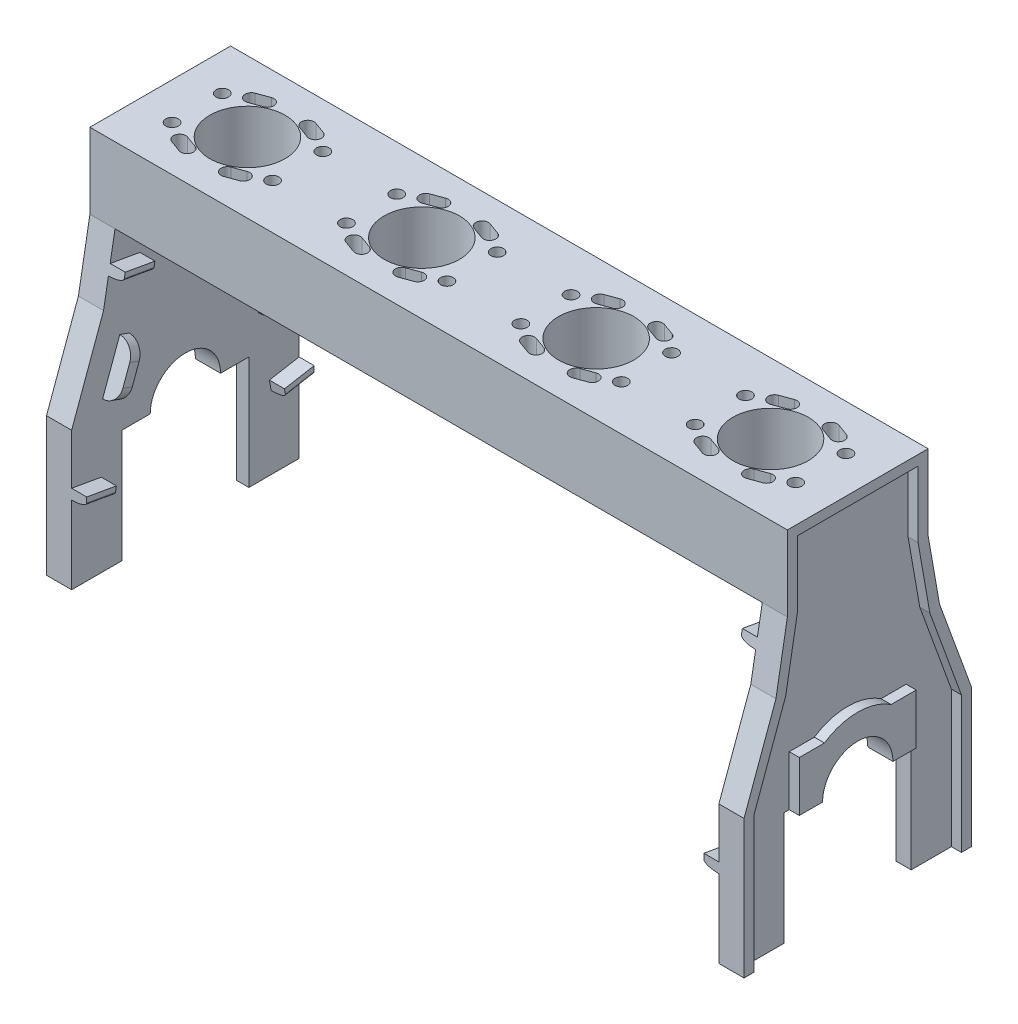
SolidWorks part; units mm, degrees
ref_plane "Front Plane" through (0, 0, 0) normal (0, 0, 1) x (1, 0, 0)
ref_plane "Top Plane" through (0, 0, 0) normal (0, 1, 0) x (1, 0, 0)
ref_plane "Right Plane" through (0, 0, 0) normal (1, 0, 0) x (0, 0, -1)
sketch "Sketch1" plane through (0, 0, 0) normal (0, 1, 0) x (1, 0, 0)
  line L0 (-313.6952, 0) -> (313.6952, 0) construction
  line L1 (-308.483, 35.56) -> (44.069, 35.56)
  line L2 (-308.483, 35.56) -> (-308.483, -35.56)
  line L3 (-308.483, -35.56) -> (44.069, -35.56)
  line L4 (44.069, 35.56) -> (44.069, -35.56)
  line L5 (0, 0) -> (0, -80.8199) construction
  line L6 (15.0411, -15.1646) -> (9.0741, -17.3365)
  line L7 (17.213, -21.1317) -> (11.2459, -23.3035)
  line L8 (16.127, -18.1482) -> (10.16, -20.32) construction
  line L9 (-17.213, -21.1317) -> (-11.2459, -23.3035)
  line L10 (-15.0411, -15.1646) -> (-9.0741, -17.3365)
  line L11 (17.213, 21.1317) -> (11.2459, 23.3035)
  line L12 (15.0411, 15.1646) -> (9.0741, 17.3365)
  line L13 (-15.0411, 15.1646) -> (-9.0741, 17.3365)
  line L14 (-17.213, 21.1317) -> (-11.2459, 23.3035)
  line L15 (-103.1791, 15.1646) -> (-97.2121, 17.3365)
  line L16 (-105.351, 21.1317) -> (-99.3839, 23.3035)
  line L17 (-70.925, 21.1317) -> (-76.8921, 23.3035)
  line L18 (-73.0969, 15.1646) -> (-79.0639, 17.3365)
  line L19 (-105.351, -21.1317) -> (-99.3839, -23.3035)
  line L20 (-103.1791, -15.1646) -> (-97.2121, -17.3365)
  line L21 (-73.0969, -15.1646) -> (-79.0639, -17.3365)
  line L22 (-70.925, -21.1317) -> (-76.8921, -23.3035)
  line L23 (-191.3171, 15.1646) -> (-185.3501, 17.3365)
  line L24 (-193.489, 21.1317) -> (-187.5219, 23.3035)
  line L25 (-159.063, 21.1317) -> (-165.0301, 23.3035)
  line L26 (-161.2349, 15.1646) -> (-167.2019, 17.3365)
  line L27 (-193.489, -21.1317) -> (-187.5219, -23.3035)
  line L28 (-191.3171, -15.1646) -> (-185.3501, -17.3365)
  line L29 (-161.2349, -15.1646) -> (-167.2019, -17.3365)
  line L30 (-159.063, -21.1317) -> (-165.0301, -23.3035)
  line L31 (-279.4551, 15.1646) -> (-273.4881, 17.3365)
  line L32 (-281.627, 21.1317) -> (-275.6599, 23.3035)
  line L33 (-247.201, 21.1317) -> (-253.1681, 23.3035)
  line L34 (-249.3729, 15.1646) -> (-255.3399, 17.3365)
  line L35 (-281.627, -21.1317) -> (-275.6599, -23.3035)
  line L36 (-279.4551, -15.1646) -> (-273.4881, -17.3365)
  line L37 (-249.3729, -15.1646) -> (-255.3399, -17.3365)
  line L38 (-247.201, -21.1317) -> (-253.1681, -23.3035)
  circle A4 centre (0, 0) radius 19.05
  circle A9 centre (-88.138, 0) radius 19.05
  circle A10 centre (-176.276, 0) radius 19.05
  circle A11 centre (-264.414, 0) radius 19.05
  circle A12 centre (25.4, -12.7) radius 3.175
  arc A17 (17.213, -21.1317) -> (15.0411, -15.1646) centre (16.127, -18.1482) ccw
  arc A18 (11.2459, -23.3035) -> (9.0741, -17.3365) centre (10.16, -20.32) cw
  circle A19 centre (-25.4, -12.7) radius 3.175
  arc A20 (-17.213, -21.1317) -> (-15.0411, -15.1646) centre (-16.127, -18.1482) cw
  arc A21 (-11.2459, -23.3035) -> (-9.0741, -17.3365) centre (-10.16, -20.32) ccw
  circle A22 centre (25.4, 12.7) radius 3.175
  arc A23 (17.213, 21.1317) -> (15.0411, 15.1646) centre (16.127, 18.1482) cw
  arc A24 (11.2459, 23.3035) -> (9.0741, 17.3365) centre (10.16, 20.32) ccw
  arc A25 (-17.213, 21.1317) -> (-15.0411, 15.1646) centre (-16.127, 18.1482) ccw
  arc A26 (-11.2459, 23.3035) -> (-9.0741, 17.3365) centre (-10.16, 20.32) cw
  circle A27 centre (-25.4, 12.7) radius 3.175
  circle A28 centre (-113.538, 12.7) radius 3.175
  arc A29 (-105.351, 21.1317) -> (-103.1791, 15.1646) centre (-104.265, 18.1482) ccw
  arc A30 (-99.3839, 23.3035) -> (-97.2121, 17.3365) centre (-98.298, 20.32) cw
  arc A31 (-76.8921, 23.3035) -> (-79.0639, 17.3365) centre (-77.978, 20.32) ccw
  arc A32 (-70.925, 21.1317) -> (-73.0969, 15.1646) centre (-72.011, 18.1482) cw
  circle A33 centre (-62.738, 12.7) radius 3.175
  arc A34 (-99.3839, -23.3035) -> (-97.2121, -17.3365) centre (-98.298, -20.32) ccw
  arc A35 (-105.351, -21.1317) -> (-103.1791, -15.1646) centre (-104.265, -18.1482) cw
  circle A36 centre (-113.538, -12.7) radius 3.175
  arc A37 (-76.8921, -23.3035) -> (-79.0639, -17.3365) centre (-77.978, -20.32) cw
  arc A38 (-70.925, -21.1317) -> (-73.0969, -15.1646) centre (-72.011, -18.1482) ccw
  circle A39 centre (-62.738, -12.7) radius 3.175
  circle A40 centre (-201.676, 12.7) radius 3.175
  arc A41 (-193.489, 21.1317) -> (-191.3171, 15.1646) centre (-192.403, 18.1482) ccw
  arc A42 (-187.5219, 23.3035) -> (-185.3501, 17.3365) centre (-186.436, 20.32) cw
  arc A43 (-165.0301, 23.3035) -> (-167.2019, 17.3365) centre (-166.116, 20.32) ccw
  arc A44 (-159.063, 21.1317) -> (-161.2349, 15.1646) centre (-160.149, 18.1482) cw
  circle A45 centre (-150.876, 12.7) radius 3.175
  arc A46 (-187.5219, -23.3035) -> (-185.3501, -17.3365) centre (-186.436, -20.32) ccw
  arc A47 (-193.489, -21.1317) -> (-191.3171, -15.1646) centre (-192.403, -18.1482) cw
  circle A48 centre (-201.676, -12.7) radius 3.175
  arc A49 (-165.0301, -23.3035) -> (-167.2019, -17.3365) centre (-166.116, -20.32) cw
  arc A50 (-159.063, -21.1317) -> (-161.2349, -15.1646) centre (-160.149, -18.1482) ccw
  circle A51 centre (-150.876, -12.7) radius 3.175
  circle A52 centre (-289.814, 12.7) radius 3.175
  arc A53 (-281.627, 21.1317) -> (-279.4551, 15.1646) centre (-280.541, 18.1482) ccw
  arc A54 (-275.6599, 23.3035) -> (-273.4881, 17.3365) centre (-274.574, 20.32) cw
  arc A55 (-253.1681, 23.3035) -> (-255.3399, 17.3365) centre (-254.254, 20.32) ccw
  arc A56 (-247.201, 21.1317) -> (-249.3729, 15.1646) centre (-248.287, 18.1482) cw
  circle A57 centre (-239.014, 12.7) radius 3.175
  arc A58 (-275.6599, -23.3035) -> (-273.4881, -17.3365) centre (-274.574, -20.32) ccw
  arc A59 (-281.627, -21.1317) -> (-279.4551, -15.1646) centre (-280.541, -18.1482) cw
  circle A60 centre (-289.814, -12.7) radius 3.175
  arc A61 (-253.1681, -23.3035) -> (-255.3399, -17.3365) centre (-254.254, -20.32) cw
  arc A62 (-247.201, -21.1317) -> (-249.3729, -15.1646) centre (-248.287, -18.1482) ccw
  circle A63 centre (-239.014, -12.7) radius 3.175
  point P16 (-308.483, 0)
  dimension "D1" = 38.1
  dimension "D2" = 88.138
  dimension "D3" = 6.35
  dimension "D4" = 35.56
  dimension "D8" = 6.35
  dimension "D10" = 10.16
  dimension "D9" = 6.35
  dimension "D16" = 4
  dimension "D5" = 44.069
  dimension "D6" = 12.7
  dimension "D7" = 25.4
  dimension "D11" = 20.32
  dimension "D12" = 70
  dimension "D13" = 62.738
  dimension "D14" = 352.552
  dimension "D15" = 4
extrude "Boss-Extrude1" add sketch "Sketch1" along normal blind 38.1
sketch "Sketch2" plane through (44.069, 0, 0) normal (1, 0, 0) x (0, 0, -1)
  line L0 (-35.56, 0) -> (-41.3634, -32.9128)
  line L1 (-35.56, 0) -> (35.56, 0) construction
  line L19 (0, -72.136) -> (0, 0) construction
  line L20 (-41.3634, -32.9128) -> (-57.4885, -77.216)
  line L21 (-57.4885, -77.216) -> (-57.4885, -147.066)
  line L22 (-17.78, -89.916) -> (-32.0885, -89.916)
  line L23 (-32.0885, -89.916) -> (-32.0885, -147.066)
  line L24 (-32.0885, -147.066) -> (-57.4885, -147.066)
  line L25 (-29.5485, -89.916) -> (-29.5485, -115.316) construction
  line L26 (17.78, -89.916) -> (32.0885, -89.916)
  line L27 (32.0885, -89.916) -> (32.0885, -147.066)
  line L28 (32.0885, -147.066) -> (57.4885, -147.066)
  line L29 (57.4885, -77.216) -> (57.4885, -147.066)
  line L30 (41.3634, -32.9128) -> (57.4885, -77.216)
  line L31 (35.56, 0) -> (41.3634, -32.9128)
  line L33 (-35.56, 0) -> (35.56, 0)
  arc A0 (17.78, -89.916) -> (-17.78, -89.916) centre (0, -89.916) ccw
  dimension "D1" = 17.78
  dimension "D2" = 71.12
  dimension "D3" = 12.7
  dimension "D5" = 170
  dimension "D7" = 25.4
  dimension "D4" = 89.916
  dimension "D6" = 2.54
  dimension "D8" = 14.3085
  dimension "D9" = 100
  dimension "D10" = 57.15
extrude "Boss-Extrude2" add sketch "Sketch2" against normal blind 12.7
sketch "Sketch3" plane through (44.069, 0, 0) normal (1, 0, 0) x (0, 0, -1)
  line L3 (-29.5485, -64.516) -> (-16.8485, -64.516)
  line L4 (16.8485, -64.516) -> (29.5485, -64.516)
  line L9 (-29.5485, -64.516) -> (-29.5485, -89.916)
  line L12 (29.5485, -64.516) -> (29.5485, -89.916)
  line L76 (0, 0) -> (0, -72.136) construction
  line L94 (-29.5485, -89.916) -> (-32.0885, -89.916)
  line L96 (-32.0885, -89.916) -> (-32.0885, -147.066)
  line L101 (-32.0885, -147.066) -> (-52.4085, -147.066)
  line L102 (29.5485, -89.916) -> (32.0885, -89.916)
  line L107 (32.0885, -89.916) -> (32.0885, -147.066) construction
  line L108 (17.78, -89.916) -> (32.0885, -89.916) construction
  line L109 (32.0885, -89.916) -> (32.0885, -147.066)
  line L110 (32.0885, -147.066) -> (57.4885, -147.066) construction
  line L111 (32.0885, -147.066) -> (52.4085, -147.066)
  line L112 (30.48, -0.4444) -> (30.48, 33.02)
  line L113 (36.4378, -34.2327) -> (30.48, -0.4444)
  line L114 (52.4085, -78.1117) -> (36.4378, -34.2327)
  line L115 (52.4085, -147.066) -> (52.4085, -78.1117)
  line L116 (-52.4085, -78.1117) -> (-52.4085, -147.066)
  line L117 (-36.4378, -34.2327) -> (-52.4085, -78.1117)
  line L118 (-30.48, -0.4444) -> (-36.4378, -34.2327)
  line L119 (-30.48, 33.02) -> (-30.48, -0.4444)
  line L120 (30.48, 33.02) -> (-30.48, 33.02)
  line L121 (30.48, -0.4444) -> (30.48, 33.02)
  line L122 (36.4378, -34.2327) -> (30.48, -0.4444)
  line L123 (52.4085, -78.1117) -> (36.4378, -34.2327)
  line L124 (52.4085, -147.066) -> (52.4085, -78.1117)
  line L125 (-52.4085, -78.1117) -> (-52.4085, -147.066)
  line L126 (-36.4378, -34.2327) -> (-52.4085, -78.1117)
  line L127 (-30.48, -0.4444) -> (-36.4378, -34.2327)
  line L128 (-30.48, 33.02) -> (-30.48, -0.4444)
  line L129 (30.48, 33.02) -> (-30.48, 33.02)
  arc A2 (16.8485, -64.516) -> (-16.8485, -64.516) centre (0, -89.916) ccw
  dimension "D6" = 25.4
  dimension "D2" = 30.48
  dimension "D3" = 25.4
  dimension "D4" = 12.7
  dimension "D5" = 12.7
  dimension "D1" = 5.08
extrude "Cut-Extrude1" cut sketch "Sketch3" against normal blind 5.08
sketch "Sketch5" plane through (-308.483, 0, 0) normal (-1, 0, 0) x (0, 0, 1)
  line L7 (17.78, -89.916) -> (32.0885, -89.916)
  line L8 (17.78, -89.916) -> (32.0885, -89.916)
  line L9 (32.0885, -89.916) -> (32.0885, -147.066)
  line L10 (35.56, 0) -> (-35.56, 0)
  line L11 (32.0885, -89.916) -> (32.0885, -147.066)
  line L12 (32.0885, -147.066) -> (57.4885, -147.066)
  line L13 (32.0885, -147.066) -> (57.4885, -147.066)
  line L17 (35.56, 0) -> (-35.56, 0)
  line L27 (57.4885, -147.066) -> (57.4885, -77.216)
  line L28 (57.4885, -147.066) -> (57.4885, -77.216)
  line L29 (57.4885, -77.216) -> (41.3634, -32.9128)
  line L30 (57.4885, -77.216) -> (41.3634, -32.9128)
  line L31 (41.3634, -32.9128) -> (35.56, 0)
  line L32 (41.3634, -32.9128) -> (35.56, 0)
  line L33 (-35.56, 0) -> (-41.3634, -32.9128)
  line L34 (-35.56, 0) -> (-41.3634, -32.9128)
  line L35 (-41.3634, -32.9128) -> (-57.4885, -77.216)
  line L36 (-41.3634, -32.9128) -> (-57.4885, -77.216)
  line L37 (-57.4885, -77.216) -> (-57.4885, -147.066)
  line L38 (-57.4885, -77.216) -> (-57.4885, -147.066)
  line L39 (-57.4885, -147.066) -> (-32.0885, -147.066)
  line L40 (-57.4885, -147.066) -> (-32.0885, -147.066)
  line L41 (-32.0885, -147.066) -> (-32.0885, -89.916)
  line L42 (-32.0885, -147.066) -> (-32.0885, -89.916)
  line L43 (-32.0885, -89.916) -> (-17.78, -89.916)
  line L44 (-32.0885, -89.916) -> (-17.78, -89.916)
  arc A1 (17.78, -89.916) -> (-17.78, -89.916) centre (0, -89.916) ccw
  arc A2 (17.78, -89.916) -> (-17.78, -89.916) centre (0, -89.916) ccw
  dimension "D1" = 0
extrude "Boss-Extrude3" add sketch "Sketch5" against normal blind 12.7
sketch "Sketch6" plane through (-308.483, 0, 0) normal (-1, 0, 0) x (0, 0, 1)
  line L4 (29.5485, -64.516) -> (29.5485, -89.916)
  line L20 (29.5485, -64.516) -> (29.5485, -89.916)
  line L21 (16.8485, -64.516) -> (29.5485, -64.516)
  line L22 (16.8485, -64.516) -> (29.5485, -64.516)
  line L24 (-29.5485, -64.516) -> (-16.8485, -64.516)
  line L25 (-29.5485, -64.516) -> (-16.8485, -64.516)
  line L39 (-29.5485, -89.916) -> (-29.5485, -64.516)
  line L40 (-29.5485, -89.916) -> (-29.5485, -64.516)
  line L41 (-32.0885, -89.916) -> (-29.5485, -89.916)
  line L42 (-32.0885, -89.916) -> (-29.5485, -89.916)
  line L43 (-32.0885, -147.066) -> (-32.0885, -89.916)
  line L44 (-32.0885, -147.066) -> (-32.0885, -89.916)
  line L45 (-52.4085, -147.066) -> (-32.0885, -147.066)
  line L46 (-52.4085, -147.066) -> (-32.0885, -147.066)
  line L47 (-52.4085, -78.1117) -> (-52.4085, -147.066)
  line L48 (-52.4085, -78.1117) -> (-52.4085, -147.066)
  line L49 (-36.4378, -34.2327) -> (-52.4085, -78.1117)
  line L50 (-36.4378, -34.2327) -> (-52.4085, -78.1117)
  line L51 (-30.48, -0.4444) -> (-36.4378, -34.2327)
  line L52 (-30.48, -0.4444) -> (-36.4378, -34.2327)
  line L53 (-30.48, 33.02) -> (-30.48, -0.4444)
  line L54 (-30.48, 33.02) -> (-30.48, -0.4444)
  line L55 (30.48, 33.02) -> (-30.48, 33.02)
  line L56 (30.48, 33.02) -> (-30.48, 33.02)
  line L57 (30.48, -0.4444) -> (30.48, 33.02)
  line L58 (30.48, -0.4444) -> (30.48, 33.02)
  line L59 (36.4378, -34.2327) -> (30.48, -0.4444)
  line L60 (36.4378, -34.2327) -> (30.48, -0.4444)
  line L61 (52.4085, -78.1117) -> (36.4378, -34.2327)
  line L62 (52.4085, -78.1117) -> (36.4378, -34.2327)
  line L63 (52.4085, -147.066) -> (52.4085, -78.1117)
  line L64 (52.4085, -147.066) -> (52.4085, -78.1117)
  line L65 (32.0885, -147.066) -> (52.4085, -147.066)
  line L66 (32.0885, -147.066) -> (52.4085, -147.066)
  line L67 (32.0885, -89.916) -> (32.0885, -147.066)
  line L68 (32.0885, -89.916) -> (32.0885, -147.066)
  line L69 (29.5485, -89.916) -> (32.0885, -89.916)
  line L70 (29.5485, -89.916) -> (32.0885, -89.916)
  arc A1 (16.8485, -64.516) -> (-16.8485, -64.516) centre (0, -89.916) ccw
  arc A3 (16.8485, -64.516) -> (-16.8485, -64.516) centre (0, -89.916) ccw
  dimension "D1" = 0
extrude "Cut-Extrude4" cut sketch "Sketch6" against normal blind 6.35
sketch "Sketch7" plane through (0, -89.916, 0) normal (0, -1, 0) x (1, 0, 0)
  line L0 (44.069, 23.1985) -> (31.369, 23.1985) construction
  line L3 (-396.1332, 0) -> (-407.4069, 0) construction
  line L5 (-132.207, 64.7886) -> (-132.207, -75.2816) construction
  line L6 (-295.783, 35.56) -> (31.369, 35.56) construction
  line L9 (44.069, 29.5485) -> (44.069, 17.78) construction
  line L10 (44.069, 29.5485) -> (44.069, 16.8485) construction
  line L11 (31.369, 32.0885) -> (31.369, 17.78) construction
  circle A0 centre (37.719, 23.1985) radius 3.175
  circle A4 centre (37.719, -23.1985) radius 3.175
  circle A5 centre (-302.133, -23.1985) radius 3.175
  circle A6 centre (-302.133, 23.1985) radius 3.175
  point P18 (-132.207, 35.56)
  point P29 (44.069, 23.1985)
  dimension "D1" = 6.35
extrude "Cut-Extrude5" cut sketch "Sketch7" against normal offset from surface (17.78 mm away) 7.62 up to face at (41.529, -64.516, 23.1985)
sketch "Sketch8" plane through (31.369, 0, 0) normal (-1, 0, 0) x (0, 0, 1)
  line L0 (-38.0206, -13.955) -> (-38.9028, -18.9578)
  line L1 (-38.9028, -18.9578) -> (-23.8943, -21.6042)
  line L2 (-23.8943, -21.6042) -> (-23.0122, -16.6014)
  line L3 (-23.0122, -16.6014) -> (-38.0206, -13.955)
  line L4 (-41.3634, -32.9128) -> (-35.56, 0) construction
  line L6 (-57.4885, -107.7744) -> (-43.3621, -110.2652)
  line L8 (-42.48, -105.2624) -> (-57.4885, -102.616)
  line L9 (-57.4885, -107.7744) -> (-57.4885, -102.616)
  line L11 (-57.4885, -147.066) -> (-57.4885, -77.216) construction
  line L12 (-42.48, -105.2624) -> (-43.3621, -110.2652)
  line L13 (-33.1482, -47.474) -> (-41.8355, -71.3422)
  line L14 (-41.8355, -71.3422) -> (-37.0619, -73.0796)
  line L15 (-37.0619, -73.0796) -> (-28.3745, -49.2114)
  line L16 (-28.3745, -49.2114) -> (-33.1482, -47.474)
  line L17 (-57.4885, -77.216) -> (-41.3634, -32.9128) construction
  line L18 (-37.4918, -59.4081) -> (-49.4259, -55.0644) construction
  line L19 (-57.4885, -77.216) -> (-57.4885, -147.066) construction
  line L20 (0, 59.5771) -> (0, 68.4397) construction
  line L21 (37.4918, -59.4081) -> (49.4259, -55.0644) construction
  line L22 (28.3745, -49.2114) -> (33.1482, -47.474)
  line L23 (37.0619, -73.0796) -> (28.3745, -49.2114)
  line L24 (41.8355, -71.3422) -> (37.0619, -73.0796)
  line L25 (33.1482, -47.474) -> (41.8355, -71.3422)
  line L26 (42.48, -105.2624) -> (43.3621, -110.2652)
  line L27 (57.4885, -107.7744) -> (57.4885, -102.616)
  line L28 (42.48, -105.2624) -> (57.4885, -102.616)
  line L29 (57.4885, -107.7744) -> (43.3621, -110.2652)
  line L30 (23.0122, -16.6014) -> (38.0206, -13.955)
  line L31 (23.8943, -21.6042) -> (23.0122, -16.6014)
  line L32 (38.9028, -18.9578) -> (23.8943, -21.6042)
  line L33 (38.0206, -13.955) -> (38.9028, -18.9578)
  point P9 (-38.4617, -16.4564)
  point P10 (-38.4617, -16.4564)
  point P25 (-49.4259, -55.0644)
  dimension "D1" = 5.08
  dimension "D2" = 15.24
  dimension "D3" = 5.08
  dimension "D4" = 15.24
  dimension "D5" = 12.7
  dimension "D6" = 5.08
  dimension "D7" = 25.4
  dimension "D8" = 25.4
extrude "Boss-Extrude4" add sketch "Sketch8" along normal blind 7.62
sketch "Sketch9" plane through (-295.783, 0, 0) normal (1, 0, 0) x (0, 0, -1)
  line L4 (43.3621, -110.2652) -> (57.4885, -107.7744)
  line L5 (42.48, -105.2624) -> (43.3621, -110.2652)
  line L6 (57.4885, -102.616) -> (42.48, -105.2624)
  line L7 (57.4885, -107.7744) -> (57.4885, -102.616)
  line L8 (43.3621, -110.2652) -> (57.4885, -107.7744)
  line L9 (42.48, -105.2624) -> (43.3621, -110.2652)
  line L10 (57.4885, -102.616) -> (42.48, -105.2624)
  line L11 (57.4885, -107.7744) -> (57.4885, -102.616)
  line L12 (38.9028, -18.9578) -> (38.0206, -13.955)
  line L13 (23.8943, -21.6042) -> (38.9028, -18.9578)
  line L14 (23.0122, -16.6014) -> (23.8943, -21.6042)
  line L15 (38.0206, -13.955) -> (23.0122, -16.6014)
  line L16 (38.9028, -18.9578) -> (38.0206, -13.955)
  line L17 (23.8943, -21.6042) -> (38.9028, -18.9578)
  line L18 (23.0122, -16.6014) -> (23.8943, -21.6042)
  line L19 (38.0206, -13.955) -> (23.0122, -16.6014)
  line L20 (41.8355, -71.3422) -> (33.1482, -47.474)
  line L21 (37.0619, -73.0796) -> (41.8355, -71.3422)
  line L22 (28.3745, -49.2114) -> (37.0619, -73.0796)
  line L23 (33.1482, -47.474) -> (28.3745, -49.2114)
  line L24 (41.8355, -71.3422) -> (33.1482, -47.474)
  line L25 (37.0619, -73.0796) -> (41.8355, -71.3422)
  line L26 (28.3745, -49.2114) -> (37.0619, -73.0796)
  line L27 (33.1482, -47.474) -> (28.3745, -49.2114)
  line L28 (-23.0122, -16.6014) -> (-38.0206, -13.955)
  line L29 (-38.0206, -13.955) -> (-38.9028, -18.9578)
  line L30 (-38.9028, -18.9578) -> (-23.8943, -21.6042)
  line L31 (-23.8943, -21.6042) -> (-23.0122, -16.6014)
  line L32 (-23.0122, -16.6014) -> (-38.0206, -13.955)
  line L33 (-38.0206, -13.955) -> (-38.9028, -18.9578)
  line L34 (-38.9028, -18.9578) -> (-23.8943, -21.6042)
  line L35 (-23.8943, -21.6042) -> (-23.0122, -16.6014)
  line L36 (-43.3621, -110.2652) -> (-42.48, -105.2624)
  line L37 (-57.4885, -107.7744) -> (-43.3621, -110.2652)
  line L38 (-57.4885, -102.616) -> (-57.4885, -107.7744)
  line L39 (-42.48, -105.2624) -> (-57.4885, -102.616)
  line L40 (-43.3621, -110.2652) -> (-42.48, -105.2624)
  line L41 (-57.4885, -107.7744) -> (-43.3621, -110.2652)
  line L42 (-57.4885, -102.616) -> (-57.4885, -107.7744)
  line L43 (-42.48, -105.2624) -> (-57.4885, -102.616)
  line L44 (-28.3745, -49.2114) -> (-33.1482, -47.474)
  line L45 (-37.0619, -73.0796) -> (-28.3745, -49.2114)
  line L46 (-41.8355, -71.3422) -> (-37.0619, -73.0796)
  line L47 (-33.1482, -47.474) -> (-41.8355, -71.3422)
  line L48 (-28.3745, -49.2114) -> (-33.1482, -47.474)
  line L49 (-37.0619, -73.0796) -> (-28.3745, -49.2114)
  line L50 (-41.8355, -71.3422) -> (-37.0619, -73.0796)
  line L51 (-33.1482, -47.474) -> (-41.8355, -71.3422)
  dimension "D1" = 0
  dimension "D2" = 0
  dimension "D3" = 0
  dimension "D4" = 0
  dimension "D5" = 0
  dimension "D6" = 0
extrude "Boss-Extrude5" add sketch "Sketch9" along normal blind 7.62
fillet "Fillet1" radius 7.62 8 edges at (23.749, -72.2109, 39.4487) (23.749, -48.3427, 30.7614) (23.749, -72.2109, -39.4487) (23.749, -48.3427, -30.7614) (-288.163, -72.2109, 39.4487) (-288.163, -48.3427, 30.7614) (-288.163, -72.2109, -39.4487) (-288.163, -48.3427, -30.7614)
fillet "Fillet2" radius 7.62 8 edges at (-288.163, -20.281, -31.3985) (-288.163, -109.0198, -50.4253) (-288.163, -109.0198, 50.4253) (-288.163, -20.281, 31.3985) (23.749, -20.281, 31.3985) (23.749, -20.281, -31.3985) (23.749, -109.0198, 50.4253) (23.749, -109.0198, -50.4253) second distance 2.54 first distance on face at (-291.973, -20.281, -31.3985) first distance on face at (-291.973, -109.0198, -50.4253) first distance on face at (-291.973, -109.0198, 50.4253) first distance on face at (-291.973, -20.281, 31.3985) first distance on face at (27.559, -20.281, 31.3985) first distance on face at (27.559, -20.281, -31.3985) first distance on face at (27.559, -109.0198, 50.4253) first distance on face at (27.559, -109.0198, -50.4253)
